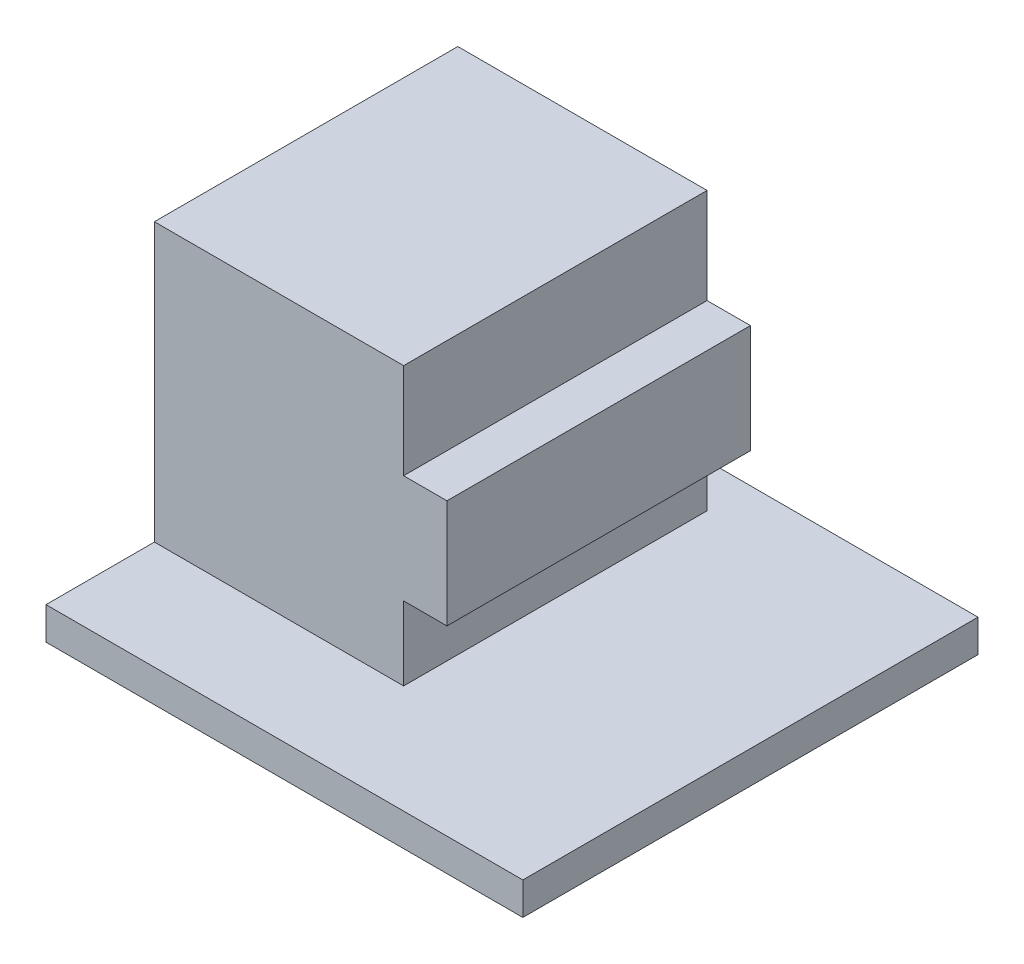
SolidWorks part; units mm, degrees
ref_plane "Front Plane" through (0, 0, 0) normal (0, 0, 1) x (1, 0, 0)
ref_plane "Top Plane" through (0, 0, 0) normal (0, 1, 0) x (1, 0, 0)
ref_plane "Right Plane" through (0, 0, 0) normal (1, 0, 0) x (0, 0, -1)
sketch "Sketch1" plane through (0, 0, 0) normal (0, 1, 0) x (1, 0, 0)
  line L1 (0, 0) -> (22, 0)
  line L2 (0, 0) -> (0, 21)
  line L3 (0, 21) -> (22, 21)
  line L4 (22, 0) -> (22, 21)
  dimension "D1" = 22
  dimension "D2" = 21
extrude "Boss-Extrude1" add sketch "Sketch1" along normal blind 1.5
ref_plane "Plane1" through (0, 0, -19) normal (0, 0, -1) x (-1, 0, 0)
sketch "Sketch3" plane through (0, 0, -19) normal (0, 0, -1) x (-1, 0, 0)
  line L0 (0, 1.5) -> (0, 14.3)
  line L1 (0, 1.5) -> (0, 0) construction
  line L2 (0, 1.5) -> (-22, 1.5) construction
  line L3 (0, 14.3) -> (-11.5, 14.3)
  line L4 (-11.5, 14.3) -> (-11.5, 9.9)
  line L5 (-11.5, 9.9) -> (-13.5, 9.9)
  line L6 (-13.5, 9.9) -> (-13.5, 4.9)
  line L7 (-13.5, 4.9) -> (-11.5, 4.9)
  line L8 (-11.5, 4.9) -> (-11.5, 1.5)
  line L9 (-11.5, 1.5) -> (0, 1.5)
  dimension "D1" = 12.8
  dimension "D2" = 11.5
  dimension "D3" = 4.4
  dimension "D4" = 2
  dimension "D5" = 5
extrude "Boss-Extrude3" add sketch "Sketch3" against normal blind 14
